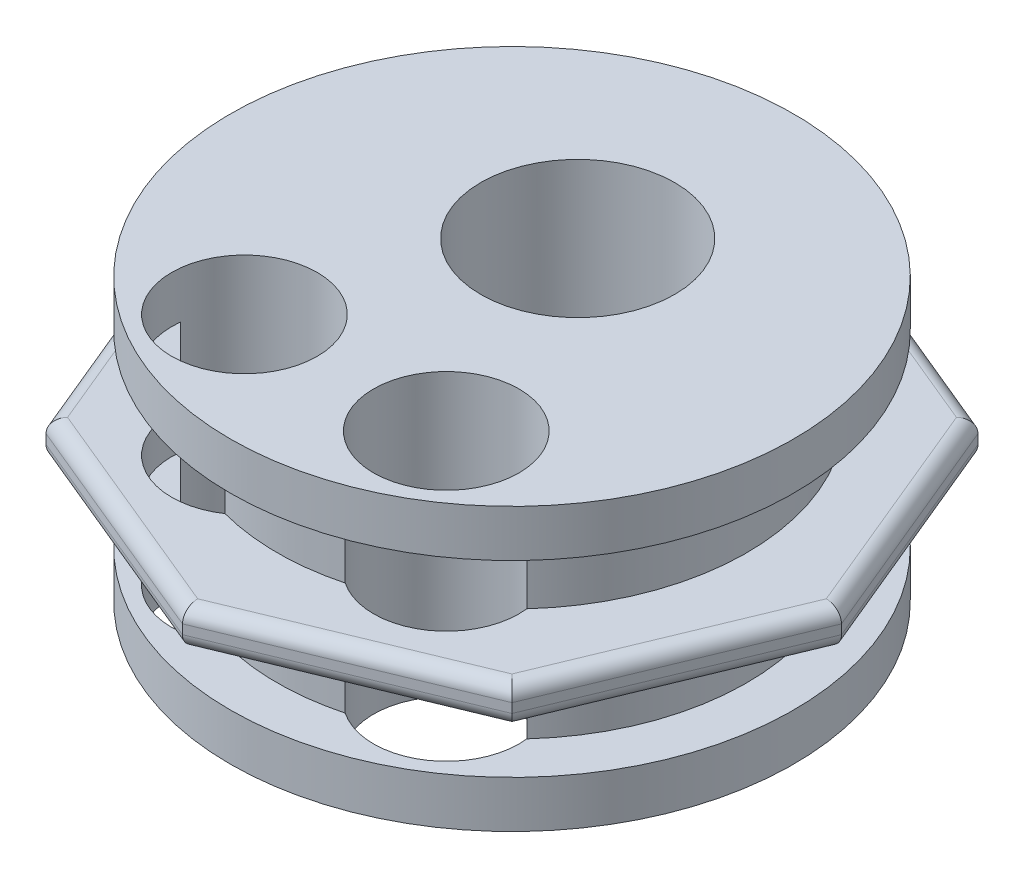
SolidWorks part; units mm, degrees
ref_plane "Front Plane" through (0, 0, 0) normal (0, 0, 1) x (1, 0, 0)
ref_plane "Top Plane" through (0, 0, 0) normal (0, 1, 0) x (1, 0, 0)
ref_plane "Right Plane" through (0, 0, 0) normal (1, 0, 0) x (0, 0, -1)
sketch "Sketch3" plane through (0, 0, 0) normal (0, 1, 0) x (1, 0, 0)
  line L1 (35.1, 0) -> (24.8194, 24.8194)
  line L2 (24.8194, 24.8194) -> (0, 35.1)
  line L3 (0, 35.1) -> (-24.8194, 24.8194)
  line L4 (-24.8194, 24.8194) -> (-35.1, 0)
  line L5 (-35.1, 0) -> (-24.8194, -24.8194)
  line L6 (-24.8194, -24.8194) -> (0, -35.1)
  line L7 (0, -35.1) -> (24.8194, -24.8194)
  line L8 (24.8194, -24.8194) -> (35.1, 0)
  circle A0 centre (0, 0) radius 32.4282 construction
  dimension "D1" = 35.1
extrude "Boss-Extrude1" add sketch "Sketch3" along normal blind 2
ref_axis "Axis2" through (0, 2, -35.1) along (0, 0, 1)
ref_axis "Axis3" through (0, 0, -35.1) along (0, 0, 1)
ref_plane "Plane1" through (0, 0, 0) normal (-1, 0, 0) x (0, 0, 1)
sketch "Sketch9" plane through (0, 2, 0) normal (0, 1, 0) x (1, 0, 0)
  line L0 (0, 38.0801) -> (0, -38.8207)
  line L1 (0, 27.2715) -> (0, -27.2715) construction
sketch "Sketch10" plane through (0, 2, 0) normal (0, 1, 0) x (1, 0, 0)
  line L1 (0, 38.0801) -> (47.253, 38.0801)
  line L2 (0, 38.0801) -> (0, -41.0679)
  line L3 (0, -41.0679) -> (47.253, -41.0679)
  line L4 (47.253, 38.0801) -> (47.253, -41.0679)
sketch "Sketch12" plane through (0, 2, 0) normal (0, 1, 0) x (1, 0, 0)
  circle A0 centre (0, 0) radius 25
extrude "Boss-Extrude2" add sketch "Sketch12" along normal blind 8 contours A0
sketch "Sketch17" plane through (0, 10, 0) normal (0, 1, 0) x (1, 0, 0)
  line L0 (0, 38.0801) -> (0, -38.8207) construction
  circle A0 centre (0, 7) radius 10.33
extrude "Cut-Extrude6" cut sketch "Sketch17" against normal blind 36 and the other way blind 9.8561 contours A0
sketch "Sketch23" plane through (0, 10, 0) normal (0, 1, 0) x (1, 0, 0)
  circle A0 centre (-10.75, -17.75) radius 7.75
  circle A1 centre (10.75, -17.75) radius 7.75
  dimension "D1" = 15.5
  dimension "D2" = 15.5
sketch "Sketch24" plane through (0, 10, 0) normal (0, 1, 0) x (1, 0, 0)
  line L2 (0, -30.0031) -> (33.426, -30.0031)
  line L3 (0, -30.0031) -> (0, 37.3911)
  line L4 (0, 37.3911) -> (33.426, 37.3911)
  line L5 (33.426, -30.0031) -> (33.426, 37.3911)
sketch "Sketch25" plane through (0, 10, 0) normal (0, 1, 0) x (1, 0, 0)
  circle A0 centre (0, 0) radius 30
  dimension "D1" = 60
extrude "Boss-Extrude3" add sketch "Sketch25" along normal blind 5
sketch "Sketch26" plane through (0, 15, 0) normal (0, 1, 0) x (1, 0, 0)
  line L0 (0, 38.0801) -> (0, -38.8207) construction
  circle A0 centre (0, 7) radius 10.33
extrude "Cut-Extrude9" cut sketch "Sketch26" against normal blind 53 contours A0
fillet "Fillet3" radius 1.5 8 edges at (12.4097, 2, 29.9597) (29.9597, 2, 12.4097) (-12.4097, 2, 29.9597) (-29.9597, 2, 12.4097) (-29.9597, 2, -12.4097) (29.9597, 2, -12.4097) (-12.4097, 2, -29.9597) (12.4097, 2, -29.9597)
extrude "Cut-Extrude11" cut sketch "Sketch23" against normal blind 36 and the other way blind 36
sketch "Sketch27" plane through (0, 15, 0) normal (0, 1, 0) x (1, 0, 0)
  line L0 (0, 38.0801) -> (0, -38.8207) construction
  point P0 (0, -10)
mirror "Mirror1" about plane through (0, 0, 0) normal (0, 1, 0) of "Boss-Extrude1", "Boss-Extrude2", "Cut-Extrude11", "Fillet3", "Cut-Extrude6", "Boss-Extrude3"
sketch "Sketch28" plane through (0, -15, 0) normal (0, -1, 0) x (1, 0, 0)
  circle A0 centre (0, -7) radius 10.33
extrude "Cut-Extrude12" cut sketch "Sketch28" against normal blind 10
